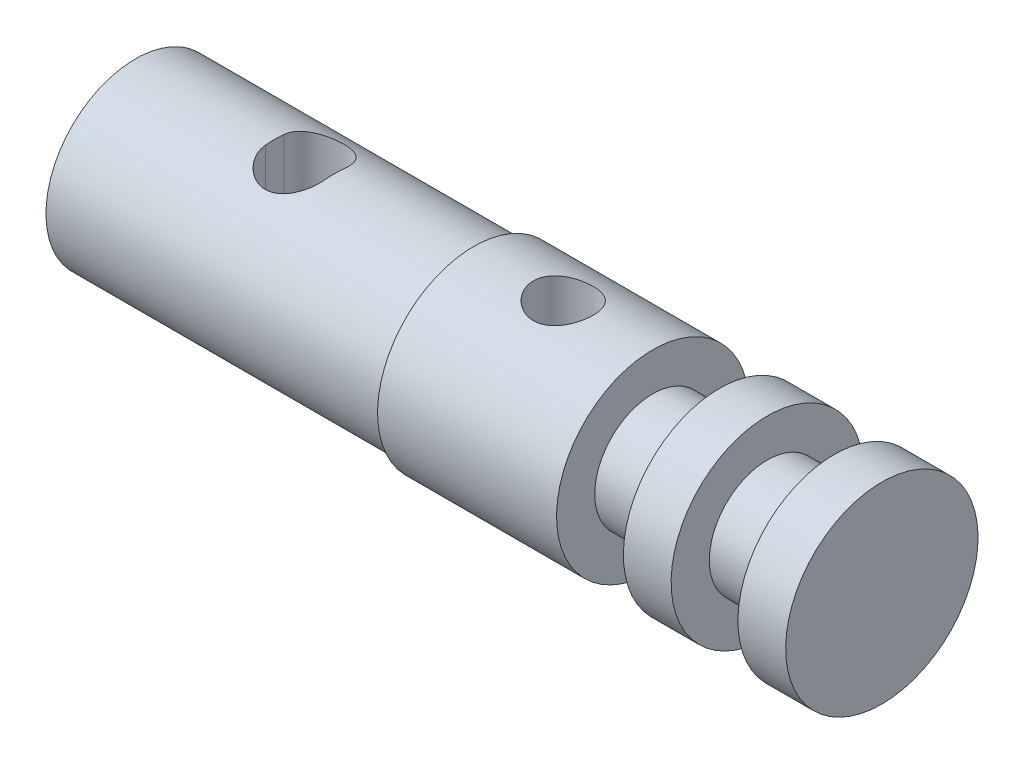
SolidWorks part; units mm, degrees
ref_plane "Front Plane" through (0, 0, 0) normal (0, 0, 1) x (1, 0, 0)
ref_plane "Top Plane" through (0, 0, 0) normal (0, 1, 0) x (1, 0, 0)
ref_plane "Right Plane" through (0, 0, 0) normal (1, 0, 0) x (0, 0, -1)
sketch "Sketch1" plane through (0, 0, 0) normal (0, 0, 1) x (1, 0, 0)
  line L0 (-19.8585, 0) -> (19.8585, 0)
  line L1 (19.8585, 0) -> (19.8585, 5.1181)
  line L2 (19.8585, 5.1181) -> (17.3185, 5.1181)
  line L3 (-1.8585, 5.1181) -> (-1.8585, 4.7625)
  line L4 (-1.8585, 4.7625) -> (-19.8585, 4.7625)
  line L5 (-19.8585, 4.7625) -> (-19.8585, 0)
  line L6 (7.6665, 5.1181) -> (7.6665, 3.0861)
  line L7 (7.6665, 3.0861) -> (11.2225, 3.0861)
  line L8 (11.2225, 3.0861) -> (11.2225, 5.1181)
  line L9 (13.7625, 5.1181) -> (13.7625, 3.0861)
  line L10 (13.7625, 3.0861) -> (17.3185, 3.0861)
  line L11 (17.3185, 3.0861) -> (17.3185, 5.1181)
  line L12 (7.6665, 5.1181) -> (-1.8585, 5.1181)
  line L13 (13.7625, 5.1181) -> (11.2225, 5.1181)
  line L14 (2.904, 5.1181) -> (2.904, 0) construction
  line L15 (1.3165, 5.1181) -> (1.3165, 0) construction
  line L16 (4.4915, 5.1181) -> (4.4915, 0) construction
  point P4 (0, 0)
  dimension "D1" = 5.1181
  dimension "D2" = 3.556
  dimension "D3" = 4.7625
  dimension "D4" = 3.0861
  dimension "D5" = 18
  dimension "D6" = 2.54
  dimension "D9" = 3.175
  dimension "D8" = 1.5875
  dimension "D7" = 1.5875
revolve "Revolve1" add sketch "Sketch1" angle 360 about L0
ref_plane "Plane1" through (0, -5.1181, 0) normal (0, -1, 0) x (-1, 0, 0)
hole_wizard "1/8 (0.125) Diameter Hole1" positions "Sketch2" profile "Sketch3" hole size "1/8" standard "ANSI Inch" end condition through all
sketch "Sketch2" plane through (0, -5.1181, 0) normal (0, -1, 0) x (-1, 0, 0)
  line L0 (-7.6665, 0) -> (1.8585, 0) construction
  line L2 (-7.6665, 5.1181) -> (-7.6665, -5.1181) construction
  line L3 (1.8585, -5.1181) -> (1.8585, 5.1181) construction
  point P0 (-2.904, 0)
  point P7 (0, 0)
  point P10 (0, 0)
  point P14 (0, 0)
sketch "Sketch3" plane through (2.904, -5.1181, 0) normal (1, 0, 0) x (0, 0, -1)
  line L0 (0, 0) -> (0, 10.2362)
  line L1 (0, 10.2362) -> (1.5875, 10.2362)
  line L2 (1.5875, 10.2362) -> (1.5875, 0)
  line L5 (1.5875, 0) -> (0, 0)
  line L11 (0, -6.35) -> (0, 107.95) construction
  dimension "Thru Hole Dia." = 3.175
  dimension "Thru Hole Depth" = 10.2362
hole_wizard "1/8 (0.1250) Dowel Slot1" positions "Sketch4" profile "Sketch5" size "1/8" standard "ANSI Inch" slot yes end condition through all
sketch "Sketch4" plane through (0, -5.1181, 0) normal (0, -1, 0) x (-1, 0, 0)
  line L0 (10.8585, -2.0875) -> (10.8585, 2.0875) construction
  line L1 (0, 0) -> (1.8585, 0) construction
  line L2 (1.8585, 0) -> (19.8585, 0) construction
  line L4 (19.8585, -4.7625) -> (19.8585, 4.7625) construction
  line L5 (1.8585, -5.1181) -> (1.8585, 5.1181) construction
  point P0 (10.8585, 0)
  point P12 (0, 0)
  point P15 (0, 0)
  point P18 (0, 0)
sketch "Sketch5" plane through (-10.8585, -5.1181, 0) normal (1, 0, 0) x (0, 0, -1)
  line L0 (0, 0) -> (0, 10.2362)
  line L1 (0, 10.2362) -> (1.5875, 10.2362)
  line L2 (1.5875, 10.2362) -> (1.5875, 0)
  line L5 (1.5875, 0) -> (0, 0)
  line L11 (0, -6.35) -> (0, 107.95) construction
  dimension "Thru Hole Dia." = 3.175
  dimension "Thru Hole Depth" = 10.2362
ref_axis "Axis1" through (-19.8585, 0, 0) along (1, 0, 0)
